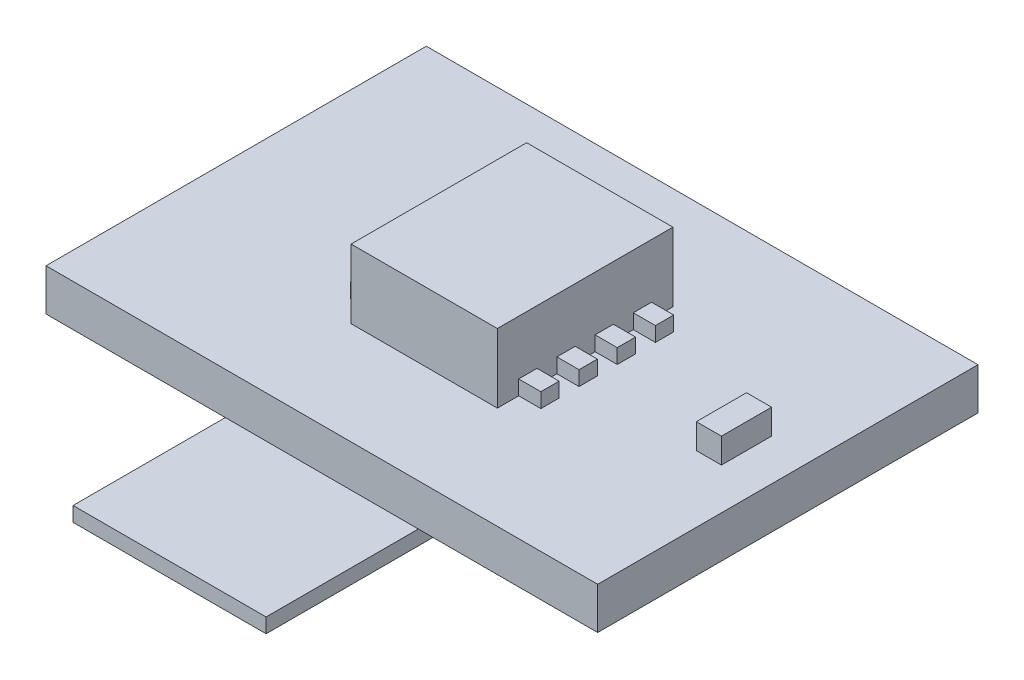
SolidWorks part; units mm, degrees
ref_plane "Спереди" through (0, 0, 0) normal (0, 0, 1) x (1, 0, 0)
ref_plane "Сверху" through (0, 0, 0) normal (0, 1, 0) x (1, 0, 0)
ref_plane "Справа" through (0, 0, 0) normal (1, 0, 0) x (0, 0, -1)
sketch "Sketch1" plane through (0, 0, 0) normal (0, 1, 0) x (1, 0, 0)
  line L1 (-6.6, 4.55) -> (6.6, 4.55)
  line L2 (-6.6, 4.55) -> (-6.6, -4.55)
  line L3 (-6.6, -4.55) -> (6.6, -4.55)
  line L4 (6.6, 4.55) -> (6.6, -4.55)
  line L5 (-6.6, 4.55) -> (6.6, -4.55) construction
  line L6 (-6.6, -4.55) -> (6.6, 4.55) construction
  point P0 (0, 0)
  dimension "D1" = 13.2
  dimension "D2" = 9.1
extrude "Boss-Extrude1" add sketch "Sketch1" along normal blind 1
sketch "Sketch2" plane through (0, 1, 0) normal (0, 1, 0) x (1, 0, 0)
  line L1 (-1.75, 2.1) -> (1.75, 2.1)
  line L2 (-1.75, 2.1) -> (-1.75, -2.1)
  line L3 (-1.75, -2.1) -> (1.75, -2.1)
  line L4 (1.75, 2.1) -> (1.75, -2.1)
  line L5 (-1.75, 2.1) -> (1.75, -2.1) construction
  line L6 (-1.75, -2.1) -> (1.75, 2.1) construction
  point P0 (0, 0)
  dimension "D1" = 3.5
  dimension "D2" = 4.2
extrude "Boss-Extrude2" add sketch "Sketch2" along normal blind 1.65
sketch "Sketch3" plane through (0, 1, 0) normal (0, 1, 0) x (1, 0, 0)
  line L1 (5.0107, 0.6) -> (5.6107, 0.6)
  line L2 (5.0107, 0.6) -> (5.0107, -0.6)
  line L3 (5.0107, -0.6) -> (5.6107, -0.6)
  line L4 (5.6107, 0.6) -> (5.6107, -0.6)
  line L5 (5.0107, 0.6) -> (5.6107, -0.6) construction
  line L6 (5.0107, -0.6) -> (5.6107, 0.6) construction
  point P0 (5.3107, 0)
  dimension "D1" = 0.6
  dimension "D2" = 1.2
extrude "Boss-Extrude3" add sketch "Sketch3" along normal blind 0.6
sketch "Sketch4" plane through (0, 0, 0) normal (0, -1, 0) x (1, 0, 0)
  line L1 (-2.3095, 8.1932) -> (2.3095, 8.1932)
  line L2 (-2.3095, 8.1932) -> (-2.3095, 0.7048)
  line L3 (-2.3095, 0.7048) -> (2.3095, 0.7048)
  line L4 (2.3095, 8.1932) -> (2.3095, 0.7048)
  line L5 (-2.3095, 8.1932) -> (2.3095, 0.7048) construction
  line L6 (-2.3095, 0.7048) -> (2.3095, 8.1932) construction
  point P0 (0, 4.449)
extrude "Boss-Extrude4" add sketch "Sketch4" along normal blind 0.35
sketch "Sketch5" plane through (0, 0, 0) normal (0, 1, 0) x (1, 0, 0)
  line L0 (0, 0) -> (0, -50000) construction
  line L1 (0, 0) -> (-50000, 0) construction
  line L2 (-1.75, 2.1) -> (-1.75, -2.1) construction
  line L3 (-1.75, 1.5896) -> (-2.2799, 1.5896)
  line L4 (-1.75, 1.5896) -> (-1.75, 1.1519)
  line L5 (-1.75, 1.1519) -> (-2.2799, 1.1519)
  line L6 (-2.2799, 1.5896) -> (-2.2799, 1.1519)
  line L7 (-2.2799, 0.238) -> (-2.2799, -0.238) construction
  line L8 (-1.75, 0.6758) -> (-2.2799, 0.6758)
  line L9 (-1.75, 0.6758) -> (-1.75, 0.238)
  line L10 (-1.75, 0.238) -> (-2.2799, 0.238)
  line L11 (-2.2799, 0.6758) -> (-2.2799, 0.238)
  line L12 (-2.2799, 1.1519) -> (-2.2799, 0.6758) construction
  line L13 (2.2799, 1.1519) -> (2.2799, 0.6758) construction
  line L14 (2.2799, 0.6758) -> (2.2799, 0.238)
  line L15 (1.75, 0.238) -> (2.2799, 0.238)
  line L16 (1.75, 0.6758) -> (1.75, 0.238)
  line L17 (1.75, 0.6758) -> (2.2799, 0.6758)
  line L18 (2.2799, 1.5896) -> (2.2799, 1.1519)
  line L19 (1.75, 1.1519) -> (2.2799, 1.1519)
  line L20 (1.75, 1.5896) -> (1.75, 1.1519)
  line L21 (1.75, 1.5896) -> (2.2799, 1.5896)
  line L22 (2.2799, -1.1519) -> (2.2799, -0.6758) construction
  line L23 (-2.2799, -1.1519) -> (-2.2799, -0.6758) construction
  line L24 (1.75, -1.5896) -> (2.2799, -1.5896)
  line L25 (1.75, -1.5896) -> (1.75, -1.1519)
  line L26 (1.75, -1.1519) -> (2.2799, -1.1519)
  line L27 (2.2799, -1.5896) -> (2.2799, -1.1519)
  line L28 (1.75, -0.6758) -> (2.2799, -0.6758)
  line L29 (1.75, -0.6758) -> (1.75, -0.238)
  line L30 (1.75, -0.238) -> (2.2799, -0.238)
  line L31 (2.2799, -0.6758) -> (2.2799, -0.238)
  line L32 (-2.2799, -0.6758) -> (-2.2799, -0.238)
  line L33 (-1.75, -0.238) -> (-2.2799, -0.238)
  line L34 (-1.75, -0.6758) -> (-1.75, -0.238)
  line L35 (-1.75, -0.6758) -> (-2.2799, -0.6758)
  line L36 (-2.2799, -1.5896) -> (-2.2799, -1.1519)
  line L37 (-1.75, -1.1519) -> (-2.2799, -1.1519)
  line L38 (-1.75, -1.5896) -> (-1.75, -1.1519)
  line L39 (-1.75, -1.5896) -> (-2.2799, -1.5896)
  point P18 (-2.2799, 0)
extrude "Boss-Extrude5" add sketch "Sketch5" along normal offset from surface (1.35 mm away) 0.35 up to face at (0, 1, 0) offset beyond the face yes
